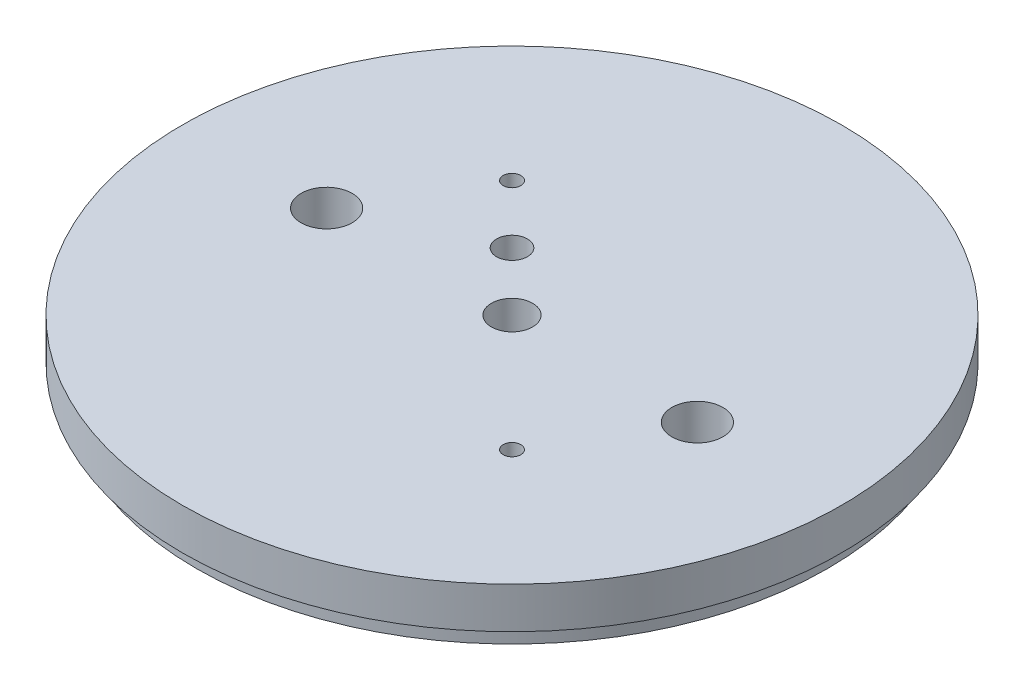
SolidWorks part; units mm, degrees
material "6061-T4 (SS)"
ref_plane "Front Plane" through (0, 0, 0) normal (0, 0, 1) x (1, 0, 0)
ref_plane "Top Plane" through (0, 0, 0) normal (0, 1, 0) x (1, 0, 0)
ref_plane "Right Plane" through (0, 0, 0) normal (1, 0, 0) x (0, 0, -1)
sketch "Sketch1" plane through (0, 0, 0) normal (0, 1, 0) x (1, 0, 0)
  line L0 (0, -50.8) -> (0, 50.8) construction
  line L1 (-50.8, 0) -> (50.8, 0) construction
  line L2 (-17.9605, 17.9605) -> (0, 0) construction
  line L3 (0, 56.7387) -> (0, 29.6936) construction
  line L4 (3.6407, 56.7387) -> (3.6407, 29.6936) construction
  line L5 (-3.6407, 56.7387) -> (-3.6407, 29.6936) construction
  line L6 (0, -56.7387) -> (0, -29.6936) construction
  line L7 (3.6407, -56.7387) -> (3.6407, -29.6936) construction
  line L8 (-3.6407, -56.7387) -> (-3.6407, -29.6936) construction
  line L9 (-35.921, -35.921) -> (54.3236, 54.3236) construction
  circle A0 centre (0, 0) radius 50.8
  circle A1 centre (0, 0) radius 3.175
  circle A2 centre (28.575, 0) radius 3.937
  circle A3 centre (-28.575, 0) radius 3.937
  circle A4 centre (-17.9605, 17.9605) radius 1.3589
  arc A6 (3.6407, 56.7387) -> (-3.6407, 56.7387) centre (0, 56.7387) ccw construction
  arc A7 (-3.6407, 29.6936) -> (3.6407, 29.6936) centre (0, 29.6936) ccw construction
  arc A8 (3.6407, -56.7387) -> (-3.6407, -56.7387) centre (0, -56.7387) cw construction
  arc A9 (-3.6407, -29.6936) -> (3.6407, -29.6936) centre (0, -29.6936) cw construction
  circle A10 centre (17.9605, -17.9605) radius 1.3589
  circle A11 centre (-8.9803, 8.9803) radius 2.3813
  circle A12 centre (8.9803, -8.9803) radius 2.3813 construction
  point P16 (0, 43.2162)
  point P19 (0, 0)
  point P26 (0, -43.2162)
  point P35 (0, 0)
  point P36 (0, 0)
  dimension "D1" = 101.6
  dimension "D2" = 6.35
  dimension "D3" = 7.874
  dimension "D5" = 2.7178
  dimension "D8" = 4.7625
  dimension "D4" = 45
  dimension "D6" = 25.4
  dimension "D7" = 45
  dimension "D9" = 28.575
extrude "Boss-Extrude1" add sketch "Sketch1" along normal blind 9.525
sketch "Sketch2" plane through (0, 0, 0) normal (0, -1, 0) x (1, 0, 0)
  circle A0 centre (0, 0) radius 50.8
  circle A1 centre (0, 0) radius 48.641
  dimension "D1" = 101.6
  dimension "D2" = 97.282
extrude "Cut-Extrude1" cut sketch "Sketch2" against normal blind 3.175
sketch "Sketch3" plane through (0, 9.525, 0) normal (0, 1, 0) x (1, 0, 0)
  line L0 (0, 50.8) -> (0, -50.8) construction
  line L1 (-50.8, 0) -> (50.8, 0) construction
  line L2 (0, 34.798) -> (0, 13.97) construction
  line L3 (3.2385, 34.798) -> (3.2385, 13.97)
  line L4 (-3.2385, 34.798) -> (-3.2385, 13.97)
  line L5 (0, -34.798) -> (0, -13.97) construction
  line L6 (3.2385, -34.798) -> (3.2385, -13.97)
  line L7 (-3.2385, -34.798) -> (-3.2385, -13.97)
  circle A0 centre (0, 0) radius 50.8 construction
  arc A1 (3.2385, 34.798) -> (-3.2385, 34.798) centre (0, 34.798) ccw
  arc A2 (-3.2385, 13.97) -> (3.2385, 13.97) centre (0, 13.97) ccw
  arc A3 (3.2385, -34.798) -> (-3.2385, -34.798) centre (0, -34.798) cw
  arc A4 (-3.2385, -13.97) -> (3.2385, -13.97) centre (0, -13.97) cw
  point P7 (0, 13.97)
  point P8 (0, 34.798)
  point P12 (0, 24.384)
  point P17 (0, 0)
  point P20 (0, -24.384)
  point P25 (0, -34.798)
  point P26 (0, -13.97)
  dimension "D1" = 13.97
  dimension "D2" = 20.828
  dimension "D3" = 6.477
extrude "Cut-Extrude2" cut sketch "Sketch3" against normal blind 3.556 from offset 5.969 offset against normal yes
equation "\"leadDist\"=1.5"
